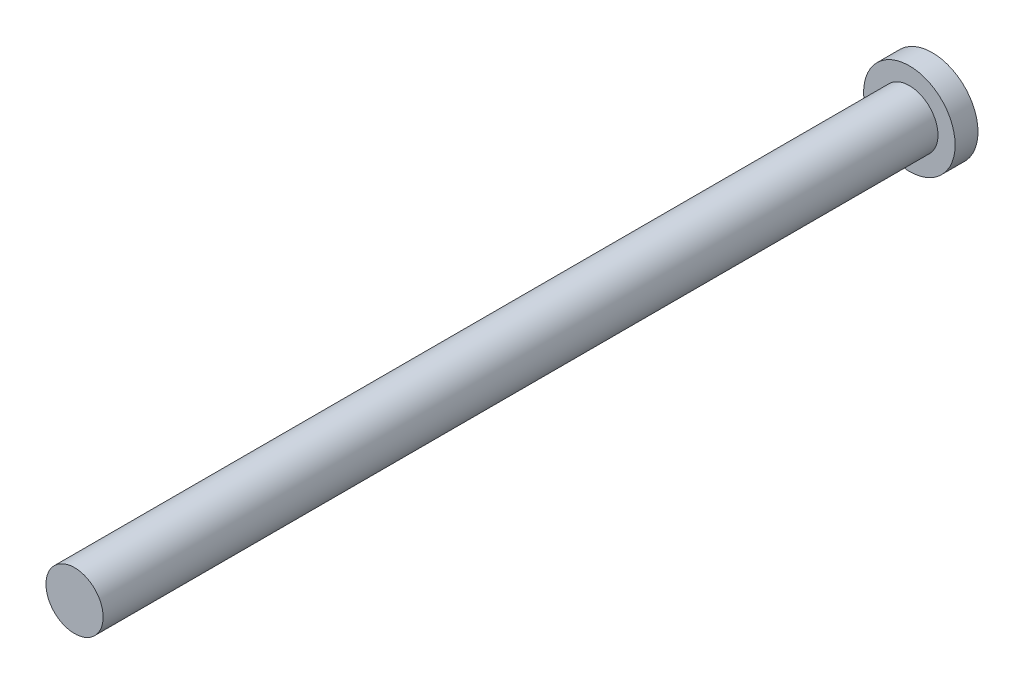
SolidWorks part; units mm, degrees
ref_plane "Plan de face" through (0, 0, 0) normal (0, 0, 1) x (1, 0, 0)
ref_plane "Plan de dessus" through (0, 0, 0) normal (0, 1, 0) x (1, 0, 0)
ref_plane "Plan de droite" through (0, 0, 0) normal (1, 0, 0) x (0, 0, -1)
sketch "Esquisse1" plane through (0, 0, 0) normal (0, 0, 1) x (1, 0, 0)
  circle A0 centre (0, 0) radius 4
  circle A1 centre (0, 0) radius 2.5
extrude "Boss.-Extru.1" add sketch "Esquisse1" along normal blind 75 contours A1 region at (0, 0, 0)
extrude "Boss.-Extru.2" add sketch "Esquisse1<3>" along normal blind 2
sketch "Esquisse1<3>" plane through (0, 0, 0) normal (0, 0, 1) x (1, 0, 0) same geometry as "Esquisse1"
sketch "Esquisse3" plane through (0, 0, 0) normal (1, 0, 0) x (0, 0, -1)
  line L0 (0, 0) -> (-75, 0)
  line L1 (0, -4) -> (0, 4) construction
  line L2 (-75, 2.5) -> (-75, -2.5) construction
  line L3 (-2, 0) -> (-75, 0)
  line L4 (-2, 4) -> (-2, -4) construction
  line L5 (-75, 2.5) -> (-75, -2.5)
  line L6 (-2, 2.5) -> (-2, -2.5)
  line L7 (-75, -2.5) -> (-2, -2.5) construction
  line L8 (0, 4) -> (0, -4)
  dimension "D1" = 5
  dimension "D2" = 75
  dimension "D3" = 73
  dimension "D4" = 8
sketch "Esquisse4" plane through (0, 0, 75) normal (0, 0, 1) x (1, 0, 0)
  circle A0 centre (0, 0) radius 2.5
  circle A1 centre (0, 0) radius 4
  dimension "D1" = 5
  dimension "D2" = 8
